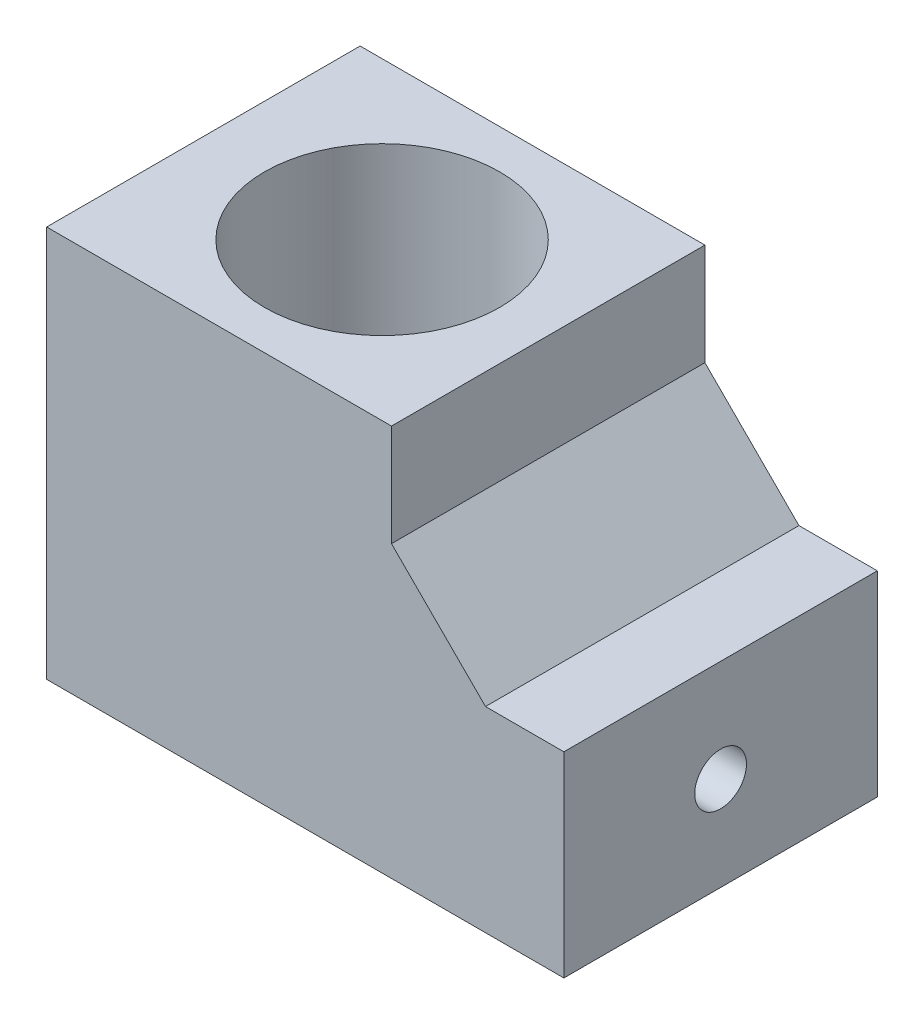
SolidWorks part; units mm, degrees
material "6061-T4 (SS)"
ref_plane "Piano frontale" through (0, 0, 0) normal (0, 0, 1) x (1, 0, 0)
ref_plane "Piano superiore" through (0, 0, 0) normal (0, 1, 0) x (1, 0, 0)
ref_plane "Piano destro" through (0, 0, 0) normal (1, 0, 0) x (0, 0, -1)
sketch "Schizzo1" plane through (0, 0, 0) normal (0, 0, 1) x (1, 0, 0)
  line L0 (0, 0) -> (33, 0)
  line L1 (33, 0) -> (33, 12.5)
  line L2 (33, 12.5) -> (28, 12.5)
  line L3 (28, 12.5) -> (22, 18.5)
  line L4 (22, 18.5) -> (22, 25)
  line L5 (22, 25) -> (0, 25)
  line L6 (0, 25) -> (0, 0)
  dimension "D1" = 33
  dimension "D2" = 22
  dimension "D3" = 25
  dimension "D4" = 12.5
  dimension "D5" = 45
  dimension "D6" = 5
extrude "Estrusione-Estrusione1" add sketch "Schizzo1" against normal blind 20
sketch "Schizzo2" plane through (0, 0, 0) normal (0, -1, 0) x (1, 0, 0)
  line L0 (0, -10) -> (33, -10) construction
  line L1 (0, -20) -> (0, 0) construction
  line L2 (33, -20) -> (33, 0) construction
  circle A0 centre (11.4, -10) radius 7.5
  dimension "D2" = 15
  dimension "D1" = 21.6
extrude "Taglio-Estrusione1" cut sketch "Schizzo2" against normal through all
sketch "Schizzo3" plane through (33, 0, 0) normal (1, 0, 0) x (0, 0, -1)
  line L0 (10, 0) -> (10, 12.5) construction
  line L1 (20, 0) -> (0, 0) construction
  line L2 (20, 12.5) -> (0, 12.5) construction
  point P6 (10, 6)
  dimension "D1" = 6
hole_wizard "Foro filettato M4-1" positions "Schizzo5" profile "Schizzo4" tap size "M4" standard "ISO"
sketch "Schizzo5" plane through (33, 0, 0) normal (1, 0, 0) x (0, 0, -1)
  point P0 (10, 6)
sketch "Schizzo4" plane through (33, 6, -10) normal (0, 1, 0) x (0, 0, -1)
  line L0 (0, 0) -> (0, 11.0914)
  line L1 (0, 11.0914) -> (1.65, 10.1)
  line L2 (1.65, 10.1) -> (1.65, 0)
  line L5 (1.65, 0) -> (0, 0)
  line L10 (0, 11.0914) -> (-1.65, 10.1) construction
  line L11 (0, -6.35) -> (0, 107.95) construction
  dimension "Tap Drill Dia." = 3.3
  dimension "Tap Drill Depth" = 10.1
  dimension "Drill Angle" = 118
cosmetic thread "Filettatura del foro1" parameters "D1"=8, "D2"=4
